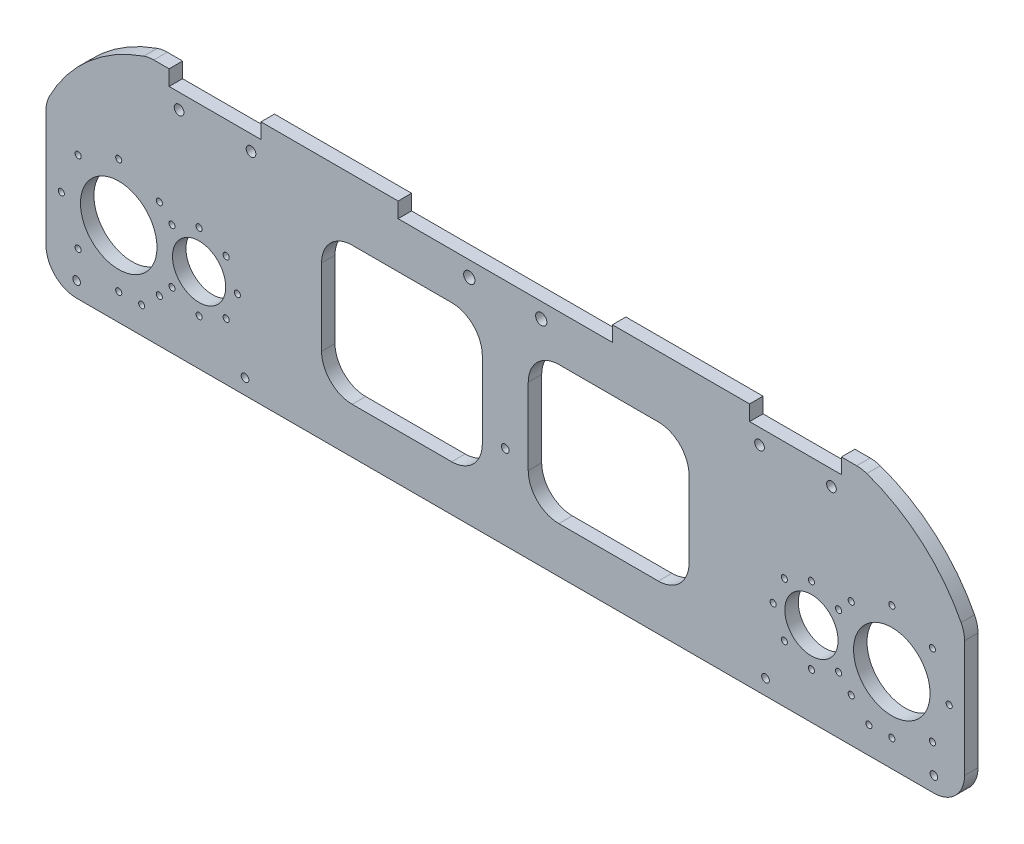
SolidWorks part; units mm, degrees
material "ABS"
ref_plane "Front Plane" through (0, 0, 0) normal (0, 0, 1) x (1, 0, 0)
ref_plane "Top Plane" through (0, 0, 0) normal (0, 1, 0) x (1, 0, 0)
ref_plane "Right Plane" through (0, 0, 0) normal (1, 0, 0) x (0, 0, -1)
sketch "Sketch1" plane through (0, 0, 0) normal (0, 0, 1) x (1, 0, 0)
  line L0 (-145.7836, 66.675) -> (145.7836, 66.675)
  line L1 (-190.5, 26.1817) -> (-190.5, -22.225)
  line L4 (0, 0) -> (0, 100.7987) construction
  line L5 (-177.8, -34.925) -> (177.8, -34.925)
  line L6 (190.5, 26.1817) -> (190.5, -22.225)
  line L7 (-190.5, 34.925) -> (190.5, -34.925) construction
  line L8 (-190.5, -34.925) -> (190.5, 34.925) construction
  arc A0 (177.8, -34.925) -> (190.5, -22.225) centre (177.8, -22.225) ccw
  arc A1 (149.9577, 65.9694) -> (189.0889, 31.9999) centre (127, 0) cw
  circle A2 centre (-127, 0) radius 3.175
  circle A3 centre (127, 0) radius 3.175
  arc A4 (-177.8, -34.925) -> (-190.5, -22.225) centre (-177.8, -22.225) cw
  arc A5 (190.5, 26.1817) -> (189.0889, 31.9999) centre (177.8, 26.1817) ccw
  arc A6 (-149.9577, 65.9694) -> (-189.0889, 31.9999) centre (-127, 0) ccw
  arc A7 (149.9577, 65.9694) -> (145.7836, 66.675) centre (145.7836, 53.975) ccw
  arc A8 (-190.5, 26.1817) -> (-189.0889, 31.9999) centre (-177.8, 26.1817) cw
  arc A9 (-145.7836, 66.675) -> (-149.9577, 65.9694) centre (-145.7836, 53.975) ccw
  point P0 (0, 0)
  point P22 (190.5, 29.0994)
  point P27 (147.8199, 66.675)
  point P30 (-190.5, 29.0994)
  point P33 (-147.8199, 66.675)
  dimension "D3" = 6.35
  dimension "D4" = 6.35
  dimension "D6" = 66.675
  dimension "D7" = 12.7
  dimension "D2" = 381
  dimension "D5" = 12.7
  dimension "D1" = 69.85
  dimension "D8" = 139.7
extrude "Boss-Extrude1" add sketch "Sketch1" along normal mid plane 5.588
sketch "Sketch2" plane through (0, 0, 2.794) normal (0, 0, 1) x (1, 0, 0)
  line L0 (-127, 0) -> (-207.737, 0) construction
  line L1 (127, 0) -> (207.737, 0) construction
  line L4 (0, 0) -> (0, 93.9723) construction
  circle A0 centre (-127, 0) radius 11.049
  circle A1 centre (-160.3375, 0) radius 15.875
  circle A2 centre (127, 0) radius 15.875 construction
  circle A3 centre (160.3375, 0) radius 23.8125 construction
  circle A4 centre (-160.3375, 0) radius 23.8125 construction
  circle A5 centre (-127, 0) radius 15.875 construction
  circle A6 centre (-160.3375, 23.8125) radius 1.27
  circle A7 centre (-143.4995, 16.838) radius 1.27
  circle A8 centre (-131.7625, 4.7625) radius 1.27 [skipped]
  circle A9 centre (-115.7747, 11.2253) radius 1.27
  circle A10 centre (-150.8125, -23.8125) radius 1.27
  circle A11 centre (-136.525, 0) radius 1.27 [skipped]
  circle A12 centre (-143.4995, -16.838) radius 1.27
  circle A13 centre (-160.3375, -23.8125) radius 1.27
  circle A14 centre (-127, 15.875) radius 1.27
  circle A15 centre (-111.125, 0) radius 1.27
  circle A16 centre (-115.7747, -11.2253) radius 1.27
  circle A17 centre (-127, -15.875) radius 1.27
  circle A18 centre (-138.2253, -11.2253) radius 1.27
  circle A19 centre (-177.1755, -16.838) radius 1.27
  circle A20 centre (177.1755, 16.838) radius 1.27
  circle A21 centre (-184.15, 0) radius 1.27
  circle A22 centre (-142.875, 0) radius 1.27 [skipped]
  circle A23 centre (138.2253, 11.2253) radius 1.27
  circle A24 centre (184.15, 0) radius 1.27
  circle A25 centre (177.1755, -16.838) radius 1.27
  circle A26 centre (138.2253, -11.2253) radius 1.27
  circle A27 centre (127, -15.875) radius 1.27
  circle A28 centre (115.7747, -11.2253) radius 1.27
  circle A29 centre (111.125, 0) radius 1.27
  circle A30 centre (127, 15.875) radius 1.27
  circle A31 centre (160.3375, -23.8125) radius 1.27
  circle A32 centre (143.4995, -16.838) radius 1.27
  circle A33 centre (150.8125, -23.8125) radius 1.27
  circle A34 centre (115.7747, 11.2253) radius 1.27
  circle A35 centre (143.4995, 16.838) radius 1.27
  circle A36 centre (160.3375, 23.8125) radius 1.27
  circle A37 centre (160.3375, 0) radius 15.875
  circle A38 centre (-175.7806, 13.4704) radius 1.27 [skipped]
  circle A39 centre (-142.1046, 20.2056) radius 1.27 [skipped]
  circle A40 centre (-138.2253, 11.2253) radius 1.27
  circle A41 centre (127, 0) radius 11.049
  circle A42 centre (-169.0454, -20.2056) radius 1.27 [skipped]
  circle A43 centre (-179.3875, -4.7625) radius 1.27 [skipped]
  circle A44 centre (-177.1755, 16.838) radius 1.27
  circle A48 centre (-135.3694, -13.4704) radius 1.27 [skipped]
  dimension "D2" = 33.3375
  dimension "D3" = 31.75
  dimension "D4" = 31.75
  dimension "D5" = 47.625
  dimension "D6" = 2.54
  dimension "D1" = 22.098
  dimension "D8" = 2.54
  dimension "D7" = 8
  dimension "D10" = 8
  dimension "D9" = 8
extrude "Cut-Extrude1" cut sketch "Sketch2" against normal through all
sketch "Sketch3" plane through (0, 0, 2.794) normal (0, 0, 1) x (1, 0, 0)
  line L0 (0, 0) -> (0, 109.3078) construction
  line L1 (145.7836, 66.675) -> (-145.7836, 66.675) construction
  line L2 (-101.3336, 66.675) -> (-139.4336, 66.675)
  line L3 (-101.3336, 66.675) -> (-101.3336, 60.325)
  line L4 (-101.3336, 60.325) -> (-139.4336, 60.325)
  line L5 (-139.4336, 66.675) -> (-139.4336, 60.325)
  line L6 (139.4336, 66.675) -> (139.4336, 60.325)
  line L7 (101.3336, 60.325) -> (139.4336, 60.325)
  line L8 (101.3336, 66.675) -> (101.3336, 60.325)
  line L9 (101.3336, 66.675) -> (139.4336, 66.675)
  line L11 (44.45, 60.325) -> (-44.45, 60.325)
  line L12 (44.45, 60.325) -> (44.45, 66.675)
  line L13 (44.45, 66.675) -> (-44.45, 66.675)
  line L14 (-44.45, 60.325) -> (-44.45, 66.675)
  line L15 (44.45, 60.325) -> (-44.45, 66.675) construction
  line L16 (44.45, 66.675) -> (-44.45, 60.325) construction
  point P13 (0, 63.5)
  dimension "D1" = 6.35
  dimension "D2" = 38.1
  dimension "D3" = 6.35
  dimension "D4" = 6.35
  dimension "D5" = 88.9
extrude "Cut-Extrude4" cut sketch "Sketch3" against normal through all
sketch "Sketch4" plane through (0, 0, 2.794) normal (0, 0, 1) x (1, 0, 0)
  line L0 (0, 93.6628) -> (0, -75.0769) construction
  line L1 (101.3336, 66.675) -> (44.45, 66.675) construction
  line L2 (-63.5, 41.275) -> (-22.225, 41.275)
  line L3 (-76.2, 28.575) -> (-76.2, -3.175)
  line L4 (-63.5, -15.875) -> (-22.225, -15.875)
  line L5 (76.2, 28.575) -> (76.2, -3.175)
  line L6 (-76.2, 41.275) -> (76.2, -15.875) construction
  line L7 (-76.2, -15.875) -> (76.2, 41.275) construction
  line L8 (-177.8, -34.925) -> (177.8, -34.925) construction
  line L9 (-9.525, 28.575) -> (-9.525, -3.175)
  line L10 (9.525, 28.575) -> (9.525, -3.175)
  line L11 (22.225, 41.275) -> (63.5, 41.275)
  line L12 (22.225, -15.875) -> (63.5, -15.875)
  arc A0 (63.5, 41.275) -> (76.2, 28.575) centre (63.5, 28.575) cw
  arc A1 (76.2, -3.175) -> (63.5, -15.875) centre (63.5, -3.175) cw
  arc A2 (-63.5, -15.875) -> (-76.2, -3.175) centre (-63.5, -3.175) cw
  arc A3 (-63.5, 41.275) -> (-76.2, 28.575) centre (-63.5, 28.575) ccw
  arc A4 (22.225, 41.275) -> (9.525, 28.575) centre (22.225, 28.575) ccw
  arc A5 (22.225, -15.875) -> (9.525, -3.175) centre (22.225, -3.175) cw
  arc A6 (-22.225, -15.875) -> (-9.525, -3.175) centre (-22.225, -3.175) ccw
  arc A7 (-22.225, 41.275) -> (-9.525, 28.575) centre (-22.225, 28.575) cw
  point P2 (0, 12.7)
  point P30 (9.525, 41.275)
  point P33 (9.525, -15.875)
  dimension "D4" = 12.7
  dimension "D7" = 12.7
  dimension "D1" = 25.4
  dimension "D2" = 19.05
  dimension "D3" = 152.4
  dimension "D5" = 9.525
  dimension "D6" = 9.525
extrude "Cut-Extrude5" cut sketch "Sketch4" against normal through all
sketch "Sketch5" plane through (0, 0, 2.794) normal (0, 0, 1) x (1, 0, 0)
  line L0 (-139.4336, 60.325) -> (-101.3336, 60.325) construction
  line L1 (-120.3836, 60.325) -> (-120.3836, 34.1975) construction
  line L2 (0, 75.8339) -> (0, -69.5106) construction
  circle A0 centre (-135.3061, 53.975) radius 2.0035
  circle A1 centre (-105.4611, 53.975) radius 2.0035
  circle A2 centre (105.4611, 53.975) radius 2.0035
  circle A3 centre (135.3061, 53.975) radius 2.0035
  circle A4 centre (-14.9225, 53.975) radius 2.3325
  circle A5 centre (14.9225, 53.975) radius 2.3325
  dimension "D1" = 6.35
  dimension "D2" = 14.9225
  dimension "D3" = 14.9225
extrude "Cut-Extrude6" cut sketch "Sketch5" against normal through all
sketch "Sketch6" plane through (0, 0, 2.794) normal (0, 0, 1) x (1, 0, 0)
  line L0 (0, 26.7131) -> (0, -52.4222) construction
  line L1 (-177.8, -34.925) -> (177.8, -34.925) construction
  circle A0 centre (-177.8, -28.575) radius 1.5875
  circle A1 centre (-107.95, -28.575) radius 1.5875
  circle A2 centre (107.95, -28.575) radius 1.5875
  circle A3 centre (177.8, -28.575) radius 1.5875
  dimension "D1" = 3.175
  dimension "D5" = 3.175
  dimension "D2" = 177.8
  dimension "D3" = 6.35
  dimension "D4" = 107.95
extrude "Cut-Extrude7" cut sketch "Sketch6" against normal through all
sketch "Sketch7" plane through (0, 0, 2.794) normal (0, 0, 1) x (1, 0, 0)
  circle A0 centre (0, 0) radius 1.5875
  dimension "D1" = 3.175
extrude "Cut-Extrude8" cut sketch "Sketch7" against normal through all
